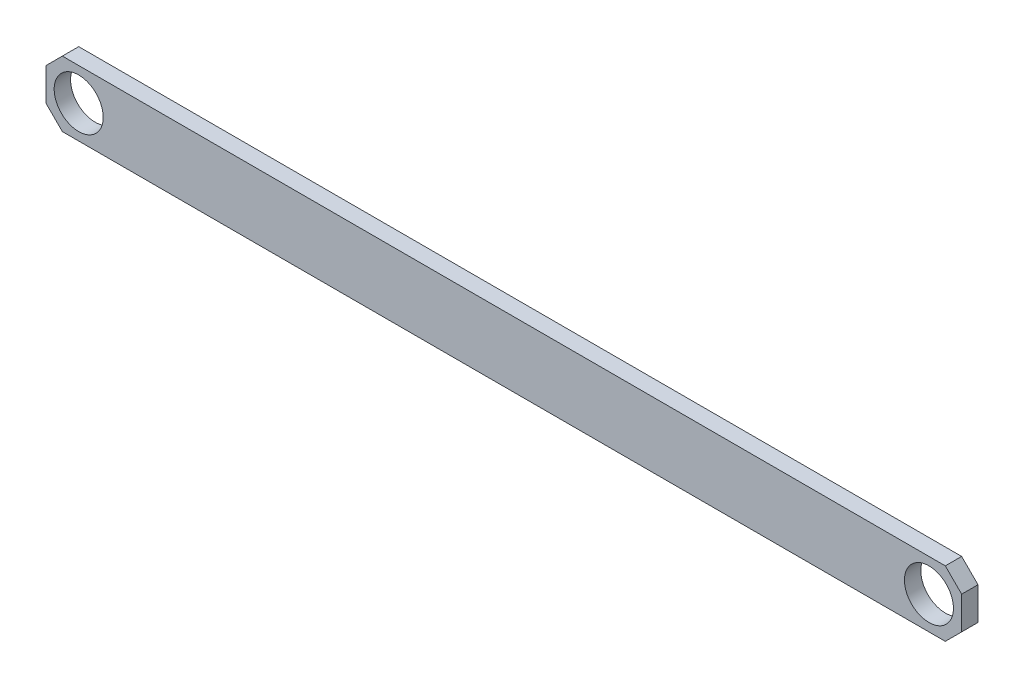
SolidWorks part; units mm, degrees
ref_plane "Front" through (0, 0, 0) normal (0, 0, 1) x (1, 0, 0)
ref_plane "Top" through (0, 0, 0) normal (0, 1, 0) x (1, 0, 0)
ref_plane "Right" through (0, 0, 0) normal (1, 0, 0) x (0, 0, -1)
sketch "Sketch1" plane through (0, 0, 0) normal (0, 0, 1) x (1, 0, 0)
  line L0 (0, 6.35) -> (27.8068, 6.35) construction
  line L1 (0, 0) -> (177.8, 0)
  line L2 (0, 0) -> (0, 12.7)
  line L3 (0, 12.7) -> (177.8, 12.7)
  line L4 (177.8, 0) -> (177.8, 12.7)
  line L5 (88.9, 0) -> (88.9, -44.6153) construction
  circle A0 centre (6.35, 6.35) radius 4.7625
  circle A1 centre (171.45, 6.35) radius 4.7625
  dimension "D3" = 9.525
  dimension "D4" = 6.35
  dimension "D1" = 12.7
  dimension "D2" = 177.8
extrude "Base-Extrude" add sketch "Sketch1" along normal blind 3.175
chamfer "Chamfer1" distance 3.175 angle 45 4 edges at (0, 12.7, 1.5875) (0, 0, 1.5875) (177.8, 0, 1.5875) (177.8, 12.7, 1.5875)
